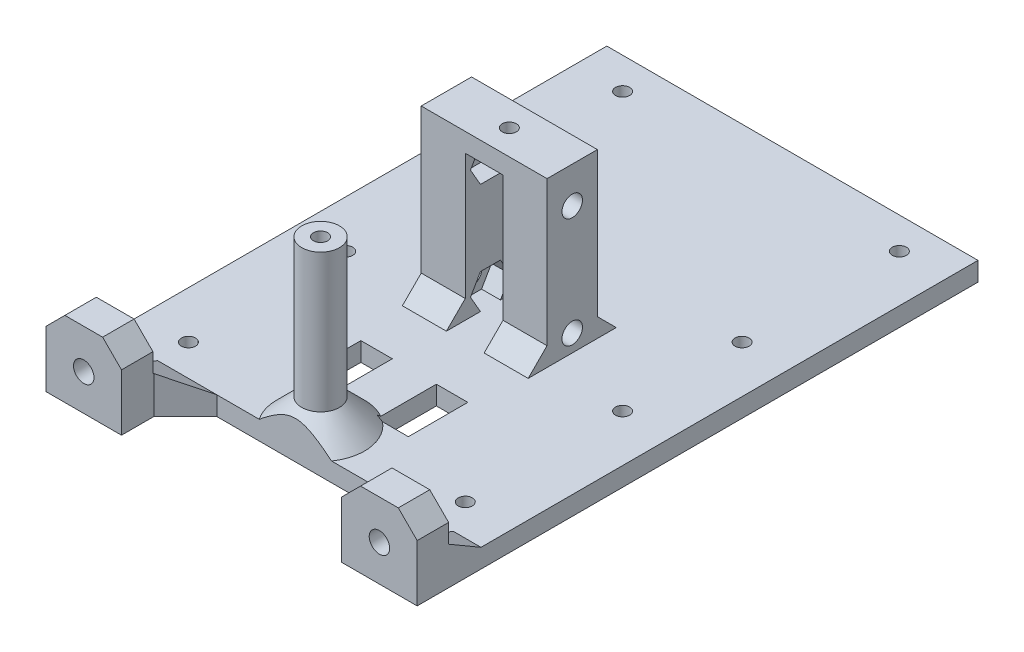
SolidWorks part; units mm, degrees
ref_plane "Alzado" through (0, 0, 0) normal (0, 0, 1) x (1, 0, 0)
ref_plane "Planta" through (0, 0, 0) normal (0, 1, 0) x (1, 0, 0)
ref_plane "Vista lateral" through (0, 0, 0) normal (1, 0, 0) x (0, 0, -1)
sketch "Croquis1" plane through (0, 0, 0) normal (0, 1, 0) x (1, 0, 0)
  line L0 (-29.5, 32.6406) -> (29.5, 32.6406)
  line L1 (29.5, 32.6406) -> (29.5, -47.3594)
  line L2 (29.5, -47.3594) -> (8.5, -47.3594)
  line L3 (8.5, -47.3594) -> (8.5, -27.4531)
  line L4 (8.5, -27.4531) -> (3.5, -27.4531)
  line L5 (3.5, -27.4531) -> (3.5, -47.3594)
  line L6 (3.5, -47.3594) -> (-3.5, -47.3594)
  line L7 (-3.5, -47.3594) -> (-3.5, -27.4531)
  line L8 (-3.5, -27.4531) -> (-8.5, -27.4531)
  line L9 (-8.5, -27.4531) -> (-8.5, -47.3594)
  line L10 (-8.5, -47.3594) -> (-29.5, -47.3594)
  line L11 (-29.5, -47.3594) -> (-29.5, 32.6406)
  line L12 (2, -7.3594) -> (47.9375, -7.3594) construction
  line L13 (0, 0) -> (0, 41.2344) construction
  dimension "D1" = 3.5
  dimension "D2" = 3.5
  dimension "D3" = 5
  dimension "D4" = 5
  dimension "D5" = 21
  dimension "D6" = 21
  dimension "D7" = 40
  dimension "D8" = 40
extrude "Base" add sketch "Croquis1" along normal blind 3
sketch "Sketch1" plane through (0, 3, 0) normal (0, 1, 0) x (1, 0, 0)
  line L0 (29.5, 32.6406) -> (-29.5, 32.6406) construction
  line L1 (-10, 23.1406) -> (10, 23.1406)
  line L2 (-10, 23.1406) -> (-10, 16.1406)
  line L3 (-10, 16.1406) -> (10, 16.1406)
  line L4 (10, 23.1406) -> (10, 16.1406)
  line L5 (-10, -8.3594) -> (10, -8.3594)
  line L6 (-10, -8.3594) -> (-10, -16.3594)
  line L7 (-10, -16.3594) -> (10, -16.3594)
  line L8 (10, -8.3594) -> (10, -16.3594)
  line L9 (0, 32.6406) -> (0, -23.7131) construction
  line L10 (8.5, -47.3594) -> (29.5, -47.3594) construction
  line L11 (3.5, -16.3594) -> (-3.5, -16.3594)
  line L12 (3.5, -16.3594) -> (3.5, -54.8594)
  line L13 (3.5, -54.8594) -> (-3.5, -54.8594)
  line L14 (-3.5, -16.3594) -> (-3.5, -54.8594)
  dimension "D1" = 9.5
  dimension "D2" = 7
  dimension "D3" = 10
  dimension "D4" = 10
  dimension "D5" = 24.5
  dimension "D6" = 8
  dimension "D7" = 10
  dimension "D8" = 10
  dimension "D9" = 7.5
extrude "Soporte Motores" add sketch "Sketch1" along normal blind 23 contours L9 L5 L6 L7 | L5 L9 L11 L7 L8 | L1 L9 L3 L4 | L9 L1 L2 L3
sketch "Sketch2" plane through (29.5, 0, 0) normal (1, 0, 0) x (0, 0, -1)
  line L0 (-54.8594, 26) -> (-46.3594, 0)
  line L1 (-47.3594, 0) -> (32.6406, 0) construction
  line L2 (-47.3594, 0) -> (-46.3594, 0)
  line L3 (-47.3594, 0) -> (-47.3594, 3)
  line L4 (-47.3594, 3) -> (-54.8594, 3)
  line L5 (-54.8594, 26) -> (-54.8594, 3)
  dimension "D1" = 1
extrude "Soporte Pala" cut sketch "Sketch2" against normal through all
sketch "Sketch3" plane through (-10, 0, 0) normal (-1, 0, 0) x (0, 0, 1)
  line L0 (8.3594, 3) -> (16.3594, 3) construction
  line L1 (16.3594, 26) -> (16.3594, 3) construction
  circle A0 centre (12.3594, 5.75) radius 1.625
  circle A1 centre (12.3594, 23.25) radius 1.625
  dimension "D1" = 3.25
  dimension "D2" = 3.25
  dimension "D3" = 2.75
  dimension "D4" = 4
  dimension "D5" = 17.5
extrude "Agujeros Motores" cut sketch "Sketch3" against normal through all
sketch "Sketch4" plane through (0, -13.6925, 41.883) normal (0, -0.3107, 0.9505) x (1, 0, 0)
  line L0 (-3.5, 14.4057) -> (3.5, 14.4057) construction
  circle A0 centre (0, 19.4057) radius 1
  circle A1 centre (0, 29.4057) radius 1
  dimension "D1" = 2
  dimension "D2" = 2
  dimension "D3" = 5
  dimension "D4" = 10
extrude "Agujeros pala" cut sketch "Sketch4" against normal blind 4
sketch "Croquis2" plane through (0, 0, -23.1406) normal (0, 0, -1) x (-1, 0, 0)
  line L0 (-10, 26) -> (-10, 3) construction
  line L1 (-5, 6) -> (-5, 3)
  line L2 (-5, 6) -> (-5, 21)
  line L3 (-5, 21) -> (5, 21)
  line L4 (5, 6) -> (5, 21)
  line L5 (10, 26) -> (10, 3) construction
  line L6 (10, 26) -> (-10, 26) construction
  line L7 (10, 3) -> (-10, 3) construction
  line L8 (5, 6) -> (5, 3)
  line L9 (5, 3) -> (-5, 3)
  dimension "D1" = 5
  dimension "D2" = 5
  dimension "D3" = 5
  dimension "D4" = 3
extrude "Hueco Soporte Posterior" cut sketch "Croquis2" against normal blind 10
sketch "Croquis3" plane through (-3.5, 0, 0) normal (-1, 0, 0) x (0, 0, 1)
  line L1 (21.9062, 3) -> (36.9062, 3)
  line L2 (21.9062, 26) -> (16.3594, 26)
  line L3 (21.9062, 26) -> (36.9062, 26)
  line L4 (36.9062, 3) -> (36.9062, 26)
  line L5 (16.3594, 26) -> (54.8594, 26) construction
  line L7 (16.3594, 26) -> (16.3594, 3)
  line L8 (16.3594, 3) -> (21.9062, 3)
  dimension "D1" = 15
extrude "Corte_Soporte_PALA_MOTOR" cut sketch "Croquis3" against normal up to next
sketch "Sketch5" plane through (-8.5, 0, 0) normal (1, 0, 0) x (0, 0, -1)
  line L0 (-36.9062, 3) -> (-36.9062, 0)
  line L1 (-46.3594, 0) -> (32.6406, 0) construction
  line L2 (-36.9062, 0) -> (-46.3594, 0)
  line L3 (-46.3594, 0) -> (-47.3401, 3)
  line L4 (-47.3401, 3) -> (-36.9062, 3)
extrude "Boss-Extrude2" add sketch "Sketch5" along normal blind 20
chamfer "Chamfer1" distance 3 angle 45 10 edges at (7.5, 3, -16.1406) (7.5, 3, -23.1406) (-5, 3, -19.6406) (5, 3, -19.6406) (-3.5, 3, 42.1232) (3.5, 3, 42.1232) (-7.5, 3, -16.1406) (-7.5, 3, -23.1406) (0, 3, 8.3594)
sketch "Croquis4" plane through (-29.5, 0, 0) normal (-1, 0, 0) x (0, 0, 1)
  line L0 (36.9062, 26) -> (36.9062, 3)
  line L1 (46.3594, 0) -> (46.3594, 3)
  line L2 (-32.6406, 3) -> (47.3401, 3) construction
  line L3 (46.3594, 3) -> (36.9062, 3)
  line L4 (46.3594, 0) -> (54.8594, 26)
  line L5 (54.8594, 26) -> (36.9062, 26)
extrude "Cortar-Extruir1" cut sketch "Croquis4" against normal through all both and the other way through all
sketch "Croquis5" plane through (-29.5, 0, 0) normal (-1, 0, 0) x (0, 0, 1)
  line L0 (46.3594, 0) -> (56.5036, 0)
  line L1 (56.5036, 0) -> (56.5036, 12)
  line L2 (56.5036, 12) -> (51.5036, 12)
  line L3 (51.5036, 12) -> (51.5036, 6)
  line L4 (51.5036, 6) -> (46.3594, 3)
  line L5 (46.3594, 0) -> (46.3594, 3) construction
  line L6 (-32.6406, 3) -> (46.3594, 3) construction
  line L7 (46.3594, 3) -> (46.3594, 0)
  dimension "D1" = 3
  dimension "D2" = 12
  dimension "D3" = 5
extrude "Saliente-Extruir1" add sketch "Croquis5" along normal blind 12 from vertex
sketch "Croquis6" plane through (-29.5, 0, 0) normal (-1, 0, 0) x (0, 0, 1)
  line L0 (46.3594, 3) -> (46.3594, 0)
  line L1 (46.3594, 0) -> (56.5036, 0)
  line L2 (56.5036, 0) -> (56.5036, 12)
  line L3 (56.5036, 12) -> (51.5036, 12)
  line L4 (51.5036, 12) -> (51.5036, 6)
  line L5 (51.5036, 6) -> (46.3594, 3) construction
  line L6 (51.5036, 12) -> (51.5036, 6) construction
  line L7 (51.5036, 6) -> (46.3594, 3)
extrude "Saliente-Extruir2" add sketch "Croquis6" against normal blind 12
chamfer "Chaflán1" distance 5 angle 45 2 edges at (-17.5, 1.5, 46.3594) (17.5, 1.5, 46.3594)
sketch "Croquis7" plane through (0, 0, 56.5036) normal (0, 0, 1) x (1, 0, 0)
  line L1 (0, 0) -> (0, 16.623) construction
  line L2 (-17.5, 0) -> (-29.5, 0) construction
  line L4 (12.5, 3) -> (-12.5, 3) construction
  circle A0 centre (-23.5, 5.75) radius 1.625
  circle A1 centre (23.5, 5.75) radius 1.625
  dimension "D1" = 3.25
  dimension "D3" = 47
  dimension "D4" = 5.75
  dimension "D2" = 2.75
extrude "Cortar-Extruir2" cut sketch "Croquis7" against normal blind 12
sketch "Croquis8" plane through (0, 0, 51.5036) normal (0, 0, -1) x (-1, 0, 0)
  line L1 (-21.9123, 3) -> (-20.3246, 5.75)
  line L2 (-20.3246, 5.75) -> (-21.9123, 8.5)
  line L3 (-21.9123, 8.5) -> (-25.0877, 8.5)
  line L4 (-25.0877, 8.5) -> (-26.6754, 5.75)
  line L5 (-26.6754, 5.75) -> (-25.0877, 3)
  line L6 (-25.0877, 3) -> (-21.9123, 3)
  line L7 (25.0877, 3) -> (26.6754, 5.75)
  line L8 (26.6754, 5.75) -> (25.0877, 8.5)
  line L9 (25.0877, 8.5) -> (21.9123, 8.5)
  line L10 (21.9123, 8.5) -> (20.3246, 5.75)
  line L11 (20.3246, 5.75) -> (21.9123, 3)
  line L12 (21.9123, 3) -> (25.0877, 3)
  circle A0 centre (-23.5, 5.75) radius 2.75 construction
  circle A1 centre (23.5, 5.75) radius 2.75 construction
  dimension "D1" = 5.5
extrude "Cortar-Extruir3" cut sketch "Croquis8" against normal blind 2.5 and the other way blind 15
sketch "Croquis10" plane through (-29.5, 0, 0) normal (-1, 0, 0) x (0, 0, 1)
  line L1 (-26.1406, 3) -> (-12.3855, 3)
  line L2 (-26.1406, 3) -> (-26.1406, 28.0148)
  line L3 (-26.1406, 28.0148) -> (-12.3855, 28.0148)
  line L4 (-12.3855, 3) -> (-12.3855, 28.0148)
extrude "Cortar-Extruir5" cut sketch "Croquis10" against normal through all both and the other way through all
sketch "Croquis11" plane through (-10, 0, 0) normal (-1, 0, 0) x (0, 0, 1)
  line L1 (8.3594, 26) -> (16.3594, 26)
  line L2 (8.3594, 26) -> (8.3594, 29)
  line L3 (8.3594, 29) -> (16.3594, 29)
  line L4 (16.3594, 26) -> (16.3594, 29)
  circle A0 centre (12.3594, 23.25) radius 1.625 construction
  dimension "D1" = 5.75
extrude "Saliente-Extruir3" add sketch "Croquis11" against normal up to vertex
sketch "Croquis12" plane through (0, 0, 8.3594) normal (0, 0, -1) x (-1, 0, 0)
  line L0 (-29.5, 3) -> (29.5, 3) construction
  line L1 (-3, 3) -> (3, 3)
  line L2 (-3, 3) -> (-3, 26)
  line L3 (-3, 26) -> (3, 26)
  line L4 (3, 3) -> (3, 26)
  line L5 (-10, 29) -> (10, 29) construction
  dimension "D1" = 3
  dimension "D2" = 6
  dimension "D3" = 3
extrude "Cortar-Extruir6" cut sketch "Croquis12" against normal up to vertex from vertex
sketch "Croquis13" plane through (3, 0, 0) normal (-1, 0, 0) x (0, 0, 1)
  line L1 (13.9471, 3) -> (15.5348, 5.75)
  line L2 (15.5348, 5.75) -> (13.9471, 8.5)
  line L3 (13.9471, 8.5) -> (10.7717, 8.5)
  line L4 (10.7717, 8.5) -> (9.1839, 5.75)
  line L5 (9.1839, 5.75) -> (10.7717, 3)
  line L6 (10.7717, 3) -> (13.9471, 3)
  line L7 (13.9471, 20.5) -> (15.5348, 23.25)
  line L8 (15.5348, 23.25) -> (13.9471, 26)
  line L9 (13.9471, 26) -> (10.7717, 26)
  line L10 (10.7717, 26) -> (9.1839, 23.25)
  line L11 (9.1839, 23.25) -> (10.7717, 20.5)
  line L12 (10.7717, 20.5) -> (13.9471, 20.5)
  circle A0 centre (12.3594, 5.75) radius 2.75 construction
  circle A1 centre (12.3594, 23.25) radius 2.75 construction
  dimension "D1" = 5.5
  dimension "D2" = 5.5
extrude "Cortar-Extruir7" cut sketch "Croquis13" against normal blind 3 and the other way blind 9
chamfer "Chaflán2" distance 3 angle 45 4 edges at (17.5, 12, 54.0036) (29.5, 12, 54.0036) (-17.5, 12, 54.0036) (-29.5, 12, 54.0036)
sketch "Croquis14" plane through (0, 3, 0) normal (0, 1, 0) x (1, 0, 0)
  line L4 (-10, -12.3594) -> (10, -12.3594) construction
  line L6 (-10, -5.3594) -> (-10, -19.3594) construction
  line L7 (10, -5.3594) -> (10, -19.3594) construction
  circle A2 centre (0, -42.3594) radius 3
  circle A3 centre (0, -42.3594) radius 1.125
  dimension "D1" = 30
  dimension "D4" = 2.25
  dimension "D5" = 6
extrude "Saliente-Extruir4" add sketch "Croquis14" along normal up to vertex (26 mm away) from vertex at 0 up to point (10, 29, 16.3594)
chamfer "Chaflán3" distance 4 angle 45 2 edges at (0, 3, 39.3594)
sketch "Croquis15" plane through (0, 29, 0) normal (0, 1, 0) x (1, 0, 0)
  circle A0 centre (0, -12.3594) radius 1.125
  dimension "D1" = 2.25
extrude "Cortar-Extruir8" cut sketch "Croquis15" against normal up to next
sketch "Croquis16" plane through (0, 3, 0) normal (0, 1, 0) x (1, 0, 0)
  line L0 (-29.5, 32.6406) -> (-29.5, -46.3594) construction
  line L1 (-12.5, -46.3594) -> (-21.9123, -46.3594) construction
  line L2 (-22, -41.3594) -> (-22, 2.6406) construction
  circle A0 centre (-22, -41.3594) radius 1.125
  circle A1 centre (22, -41.3594) radius 1.125
  circle A2 centre (-22, 2.6406) radius 1.125
  circle A3 centre (22, 2.6406) radius 1.125
  circle A4 centre (-22, 27.6406) radius 1.125
  circle A5 centre (22, 27.6406) radius 1.125
  circle A6 centre (-22, -16.3594) radius 1.125
  circle A7 centre (22, -16.3594) radius 1.125
  dimension "D1" = 2.25
  dimension "D4" = 5
  dimension "D2" = 44
  dimension "D3" = 7.5
  dimension "D6" = 44
  dimension "D5" = 2
  dimension "D7" = 2
  dimension "D8" = 2
extrude "Cortar-Extruir9" cut sketch "Croquis16" against normal through all
